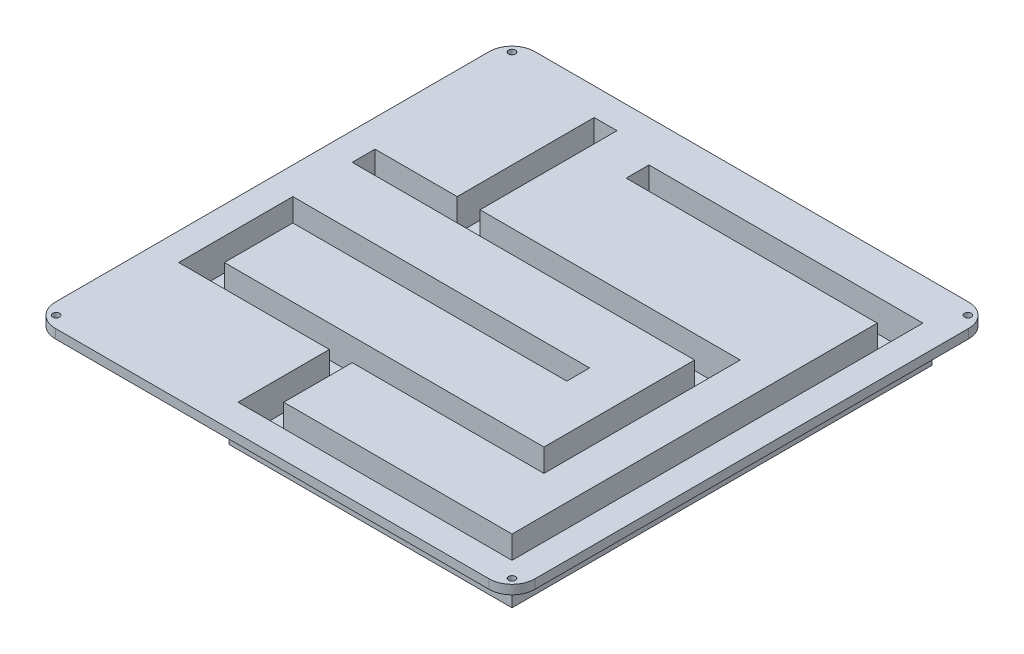
SolidWorks part; units mm, degrees
ref_plane "Front Plane" through (0, 0, 0) normal (0, 0, 1) x (1, 0, 0)
ref_plane "Top Plane" through (0, 0, 0) normal (0, 1, 0) x (1, 0, 0)
ref_plane "Right Plane" through (0, 0, 0) normal (1, 0, 0) x (0, 0, -1)
sketch "Sketch1" plane through (0, 0, 0) normal (0, 1, 0) x (1, 0, 0)
  line L0 (-101, -101) -> (-101, 101)
  line L5 (-105, -105) -> (105, -105)
  line L6 (-105, -105) -> (-105, 105)
  line L7 (-105, 105) -> (105, 105)
  line L8 (105, -105) -> (105, 105)
  line L9 (-101, 101) -> (101, 101)
  line L10 (101, -101) -> (101, 101)
  line L11 (-101, -101) -> (101, -101)
  line L12 (-101, 101) -> (-99.8333, 99.8333) construction
  line L13 (-55, 0) -> (55, 0) construction
  line L14 (-101, -101) -> (-99.8333, -99.8333) construction
  line L15 (0, -55) -> (0, 55) construction
  line L16 (101, -101) -> (99.8333, -99.8333) construction
  line L17 (101, 101) -> (99.8333, 99.8333) construction
  circle A1 centre (-99.8333, 99.8333) radius 1.5
  circle A2 centre (-99.8333, -99.8333) radius 1.5
  circle A3 centre (99.8333, -99.8333) radius 1.5
  circle A4 centre (99.8333, 99.8333) radius 1.5
  point P0 (0, 0)
  point P6 (-105, 0)
  point P7 (0, 105)
  dimension "D3" = 4
  dimension "D4" = 3
  dimension "D1" = 210
  dimension "D2" = 210
  dimension "D5" = 1.65
  dimension "D6" = 45
extrude "MainExtrude" add sketch "Sketch1" along normal blind 4 contours L6 L5 L8 L7
extrude "ScrewHoles" cut sketch "Sketch1<6>" along normal up to surface (4 mm away) contours A1 | A2 | A3 | A4 up to face at (0, 4, 0)
sketch "Sketch1<6>" plane through (0, 0, 0) normal (0, 1, 0) x (1, 0, 0) same geometry as "Sketch1"
fillet "RoundedCorners" radius 10 4 edges at (-105, 2, -105) (-105, 2, 105) (105, 2, -105) (105, 2, 105)
sketch "Sketch3" plane through (0, 0, 0) normal (0, 1, 0) x (1, 0, 0)
  line L24 (-52, 93) -> (-52, 33) construction
  line L25 (-57, 93) -> (-57, 33)
  line L58 (-93, 28) -> (62, 28) construction
  line L59 (62, 28) -> (62, -48) construction
  line L60 (62, -48) -> (-88, -48) construction
  line L61 (-88, -48) -> (-88, -8) construction
  line L62 (-88, -8) -> (37, -8) construction
  line L63 (-22, -53) -> (-22, -88) construction
  line L64 (-22, -88) -> (88, -88) construction
  line L65 (88, -88) -> (88, 82) construction
  line L66 (88, 82) -> (-27, 82) construction
  line L68 (-93, 23) -> (57, 23)
  line L69 (57, 23) -> (57, -43)
  line L70 (57, -43) -> (-83, -43)
  line L71 (-83, -43) -> (-83, -13)
  line L72 (-83, -13) -> (37, -13)
  line L73 (-27, -53) -> (-27, -93)
  line L74 (-27, -93) -> (93, -93)
  line L75 (93, -93) -> (93, 87)
  line L76 (93, 87) -> (-27, 87)
  line L77 (-47, 93) -> (-47, 33)
  line L78 (-93, 33) -> (-57, 33)
  line L79 (67, 33) -> (67, -53)
  line L80 (67, -53) -> (-17, -53)
  line L81 (-93, -53) -> (-93, -3)
  line L82 (-93, -3) -> (37, -3)
  line L83 (-17, -53) -> (-17, -83)
  line L84 (-17, -83) -> (83, -83)
  line L85 (83, -83) -> (83, 77)
  line L86 (83, 77) -> (-27, 77)
  line L87 (-57, 93) -> (-47, 93)
  line L89 (-93, 23) -> (-93, 33)
  line L90 (37, -13) -> (37, -3)
  line L92 (-27, 87) -> (-27, 77)
  line L93 (-47, 93) -> (-47, 31.8434) construction
  line L94 (-52, 93) -> (-52, 31.8434) construction
  line L95 (-57, 93) -> (-57, 31.8434) construction
  line L96 (-17, 9.5948) -> (-17, -83) construction
  line L97 (-22, 9.5948) -> (-22, -88) construction
  line L98 (-27, 9.5948) -> (-27, -93) construction
  line L99 (-27, -53) -> (-93, -53)
  line L100 (67, -53) -> (-93, -53) construction
  line L101 (-47, 33) -> (67, 33)
  line L102 (-93, 33) -> (67, 33) construction
  line L106 (-105, -95) -> (-105, 95) construction
  line L107 (-95, -105) -> (95, -105) construction
  line L108 (-95, 105) -> (95, 105) construction
  line L109 (105, -95) -> (105, 95) construction
  dimension "D1" = 5
  dimension "D2" = 5
  dimension "D3" = 12
  dimension "D4" = 12
  dimension "D5" = 12
  dimension "D6" = 12
  dimension "D7" = 60
  dimension "D8" = 160
  dimension "D9" = 130
  dimension "D11" = 120
  dimension "D13" = 30
  dimension "D14" = 120
  dimension "D10" = 30
  dimension "D12" = 160
  dimension "D15" = 20
  dimension "D17" = 160
  dimension "D16" = 66
extrude "Trench" cut sketch "Sketch3" along normal blind 12
sketch "Sketch7" plane through (0, 0, 0) normal (0, -1, 0) x (1, 0, 0)
  line L0 (-59, -95) -> (-45, -95)
  line L1 (-45, -95) -> (-45, -35)
  line L2 (-45, -35) -> (69, -35)
  line L3 (69, -35) -> (69, 55)
  line L5 (69, 55) -> (-15, 55)
  line L6 (-15, 55) -> (-15, 81)
  line L7 (-15, 81) -> (81, 81)
  line L12 (81, 81) -> (81, -75)
  line L13 (81, -75) -> (-29, -75)
  line L14 (-29, -75) -> (-29, -89)
  line L15 (-29, -89) -> (95, -89)
  line L16 (95, -89) -> (95, 95)
  line L17 (95, 95) -> (-29, 95)
  line L18 (-29, 95) -> (-29, 55)
  line L19 (-29, 55) -> (-95, 55)
  line L20 (-95, 55) -> (-95, 1)
  line L21 (-95, 1) -> (39, 1)
  line L22 (39, 1) -> (39, 15)
  line L23 (39, 15) -> (-81, 15)
  line L24 (-81, 15) -> (-81, 41)
  line L25 (-81, 41) -> (55, 41)
  line L26 (55, 41) -> (55, -21)
  line L27 (55, -21) -> (-95, -21)
  line L28 (-95, -21) -> (-95, -35)
  line L29 (-95, -35) -> (-59, -35)
  line L30 (-59, -35) -> (-59, -95)
  line L31 (-57, -93) -> (-47, -93)
  line L32 (-57, -33) -> (-57, -93)
  line L33 (-93, -33) -> (-57, -33)
  line L34 (-93, -23) -> (-93, -33)
  line L35 (57, -23) -> (-93, -23)
  line L36 (57, 43) -> (57, -23)
  line L37 (-83, 43) -> (57, 43)
  line L38 (-83, 13) -> (-83, 43)
  line L39 (37, 13) -> (-83, 13)
  line L40 (37, 3) -> (37, 13)
  line L41 (-93, 3) -> (37, 3)
  line L42 (-93, 53) -> (-93, 3)
  line L43 (-27, 53) -> (-93, 53)
  line L44 (-27, 93) -> (-27, 53)
  line L45 (93, 93) -> (-27, 93)
  line L46 (93, -87) -> (93, 93)
  line L47 (-27, -87) -> (93, -87)
  line L48 (-27, -77) -> (-27, -87)
  line L49 (83, -77) -> (-27, -77)
  line L50 (83, 83) -> (83, -77)
  line L51 (-17, 83) -> (83, 83)
  line L52 (-17, 53) -> (-17, 83)
  line L53 (67, 53) -> (-17, 53)
  line L54 (67, -33) -> (67, 53)
  line L55 (-47, -33) -> (67, -33)
  line L56 (-47, -93) -> (-47, -33)
  line L57 (-57, -93) -> (-47, -93)
  line L58 (-57, -33) -> (-57, -93)
  line L59 (-93, -33) -> (-57, -33)
  line L60 (-93, -23) -> (-93, -33)
  line L61 (57, -23) -> (-93, -23)
  line L62 (57, 43) -> (57, -23)
  line L63 (-83, 43) -> (57, 43)
  line L64 (-83, 13) -> (-83, 43)
  line L65 (37, 13) -> (-83, 13)
  line L66 (37, 3) -> (37, 13)
  line L67 (-93, 3) -> (37, 3)
  line L68 (-93, 53) -> (-93, 3)
  line L69 (-27, 53) -> (-93, 53)
  line L70 (-27, 93) -> (-27, 53)
  line L71 (93, 93) -> (-27, 93)
  line L72 (93, -87) -> (93, 93)
  line L73 (-27, -87) -> (93, -87)
  line L74 (-27, -77) -> (-27, -87)
  line L75 (83, -77) -> (-27, -77)
  line L76 (83, 83) -> (83, -77)
  line L77 (-17, 83) -> (83, 83)
  line L78 (-17, 53) -> (-17, 83)
  line L79 (67, 53) -> (-17, 53)
  line L80 (67, -33) -> (67, 53)
  line L81 (-47, -33) -> (67, -33)
  line L82 (-47, -93) -> (-47, -33)
  dimension "D1" = 0
  dimension "D2" = 2
extrude "Trench Walls" add sketch "Sketch7" along normal blind 10
sketch "Sketch8" plane through (0, -10, 0) normal (0, -1, 0) x (1, 0, 0)
  line L26 (-59, -35) -> (-59, -95)
  line L27 (-59, -95) -> (-45, -95)
  line L28 (-45, -95) -> (-45, -35)
  line L29 (-45, -35) -> (69, -35)
  line L30 (69, -35) -> (69, 55)
  line L31 (69, 55) -> (-15, 55)
  line L32 (-15, 55) -> (-15, 81)
  line L33 (-15, 81) -> (81, 81)
  line L34 (81, 81) -> (81, -75)
  line L35 (81, -75) -> (-29, -75)
  line L36 (-29, -75) -> (-29, -89)
  line L37 (-29, -89) -> (95, -89)
  line L38 (95, -89) -> (95, 95)
  line L39 (95, 95) -> (-29, 95)
  line L40 (-29, 95) -> (-29, 55)
  line L41 (-29, 55) -> (-95, 55)
  line L42 (-95, 55) -> (-95, 1)
  line L43 (-95, 1) -> (39, 1)
  line L44 (39, 1) -> (39, 15)
  line L45 (39, 15) -> (-81, 15)
  line L46 (-81, 15) -> (-81, 41)
  line L47 (-81, 41) -> (55, 41)
  line L48 (55, 41) -> (55, -21)
  line L49 (55, -21) -> (-95, -21)
  line L50 (-95, -21) -> (-95, -35)
  line L51 (-95, -35) -> (-59, -35)
  line L52 (-59, -35) -> (-59, -95)
  line L53 (-59, -95) -> (-45, -95)
  line L54 (-45, -95) -> (-45, -35)
  line L55 (-45, -35) -> (69, -35)
  line L56 (69, -35) -> (69, 55)
  line L57 (69, 55) -> (-15, 55)
  line L58 (-15, 55) -> (-15, 81)
  line L59 (-15, 81) -> (81, 81)
  line L60 (81, 81) -> (81, -75)
  line L61 (81, -75) -> (-29, -75)
  line L62 (-29, -75) -> (-29, -89)
  line L63 (-29, -89) -> (95, -89)
  line L64 (95, -89) -> (95, 95)
  line L65 (95, 95) -> (-29, 95)
  line L66 (-29, 95) -> (-29, 55)
  line L67 (-29, 55) -> (-95, 55)
  line L68 (-95, 55) -> (-95, 1)
  line L69 (-95, 1) -> (39, 1)
  line L70 (39, 1) -> (39, 15)
  line L71 (39, 15) -> (-81, 15)
  line L72 (-81, 15) -> (-81, 41)
  line L73 (-81, 41) -> (55, 41)
  line L74 (55, 41) -> (55, -21)
  line L75 (55, -21) -> (-95, -21)
  line L76 (-95, -21) -> (-95, -35)
  line L77 (-95, -35) -> (-59, -35)
  dimension "D1" = 0
extrude "Trench Bottom" add sketch "Sketch8" along normal blind 2
